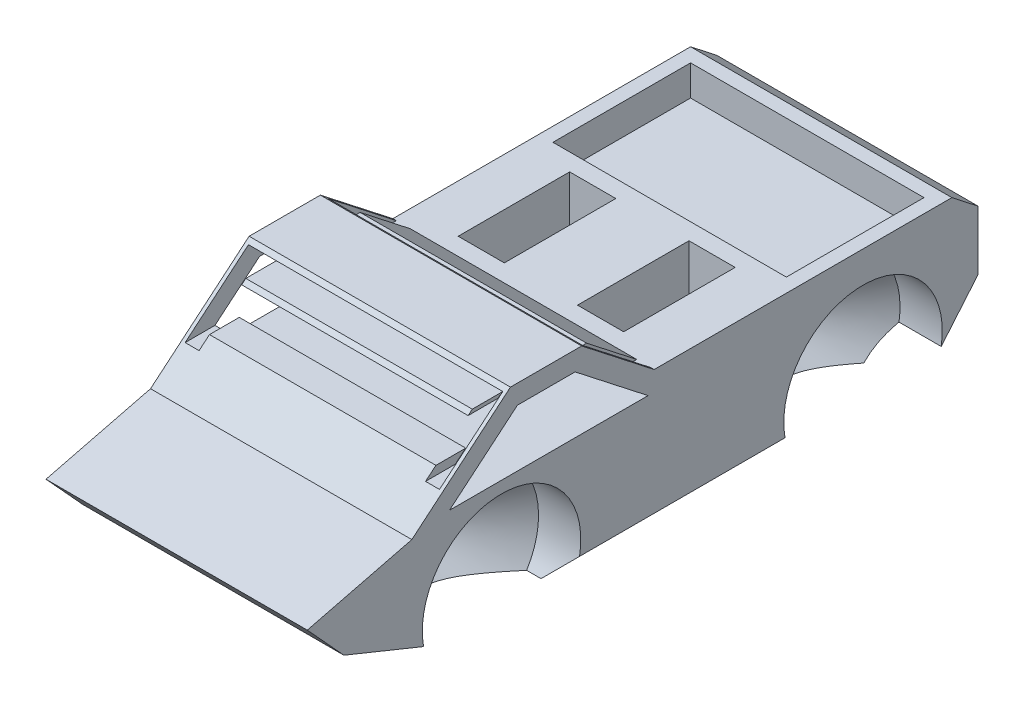
SolidWorks part; units mm, degrees
material "AISI 316 Stainless Steel Sheet (SS)"
ref_plane "Front Plane" through (0, 0, 0) normal (0, 0, 1) x (1, 0, 0)
ref_plane "Top Plane" through (0, 0, 0) normal (0, 1, 0) x (1, 0, 0)
ref_plane "Right Plane" through (0, 0, 0) normal (1, 0, 0) x (0, 0, -1)
sketch "Sketch1" plane through (0, 0, 0) normal (1, 0, 0) x (0, 0, -1)
  line L0 (0, 0) -> (12, 3)
  line L1 (12, 3) -> (23.3217, 12.5)
  line L2 (23.3217, 12.5) -> (31.5, 12.5)
  line L3 (31.5, 12.5) -> (39.8196, 6)
  line L4 (39.8196, 6) -> (74, 6)
  line L5 (74, 6) -> (77, 3.6561)
  line L6 (77, 3.6561) -> (77, -3.1577)
  line L7 (77, -3.1577) -> (70, -11.5)
  line L8 (70, -11.5) -> (16, -11.5)
  line L9 (16, -11.5) -> (13.3149, -8.3)
  line L10 (13.3149, -8.3) -> (4.2, -4.6)
  line L11 (4.2, -4.6) -> (0, 0)
  line L12 (16.3211, 3.754) -> (24.1224, 10.3)
  line L13 (24.1224, 10.3) -> (30.7425, 10.3)
  line L14 (30.7425, 10.3) -> (39.121, 3.754)
  line L15 (30.7425, 10.3) -> (38.4652, 4.2664) construction
  line L17 (13.4141, 1.3147) -> (24.1224, 10.3) construction
  line L18 (16.3211, 3.754) -> (39.121, 3.754)
  dimension "D1" = 12
  dimension "D2" = 31.5
  dimension "D3" = 24
  dimension "D4" = 40
  dimension "D5" = 38
  dimension "D6" = 3
  dimension "D7" = 17.5
  dimension "D8" = 7
  dimension "D9" = 130
  dimension "D10" = 77
  dimension "D11" = 16
  dimension "D12" = 3.2
  dimension "D13" = 4.2
  dimension "D14" = 4.6
  dimension "D15" = 11.5
  dimension "D16" = 3
  dimension "D18" = 22.7999
  dimension "D19" = 2.2
  dimension "D17" = 2.2
extrude "Boss-Extrude1" add sketch "Sketch1" along normal mid plane 30
chamfer "Chamfer1" distance 3.2 angle 45 2 edges at (-15, -11.5, -43) (15, -11.5, -43)
ref_plane "Plane1" through (0, 0, -22.3) normal (0, 0, 1) x (1, 0, 0)
sketch "Sketch2" plane through (0, 0, -22.3) normal (0, 0, 1) x (1, 0, 0)
  line L0 (15, 2.4) -> (10.15, 2.4)
  line L1 (15, 3) -> (15, 0) construction
  line L2 (10.15, 2.4) -> (3.75, -4)
  line L3 (3.75, -4) -> (0, -4)
  line L4 (0, -4) -> (0, -6.7)
  line L5 (0, -6.7) -> (15, -6.7)
  line L6 (15, -4.6) -> (15, -8.3) construction
  line L7 (15, -6.7) -> (15, 2.4)
  line L8 (0, -6.7) -> (-8.558, -6.7) construction
  dimension "D1" = 5.4
  dimension "D2" = 45
  dimension "D3" = 3.75
  dimension "D4" = 6.7
  dimension "D5" = 18.2
revolve "Cut-Revolve1" cut sketch "Sketch2" angle 360 about L8
mirror "Mirror1" about plane through (0, 0, 0) normal (1, 0, 0) of "Cut-Revolve1"
pattern_linear "LPattern1" count 2 spacing 41.5 along (0, 0, -1) of "Cut-Revolve1"
mirror "Mirror2" about plane through (0, 0, 0) normal (1, 0, 0) of "LPattern1"
sketch "Sketch4" plane through (0, 6, 0) normal (0, 1, 0) x (1, 0, 0)
  line L0 (15, 74) -> (15, 39.8196) construction
  line L1 (4.2, 54.6196) -> (9.5, 54.6196)
  line L2 (4.2, 54.6196) -> (4.2, 41.8196)
  line L3 (4.2, 41.8196) -> (9.5, 41.8196)
  line L4 (9.5, 54.6196) -> (9.5, 41.8196)
  line L5 (15, 39.8196) -> (-15, 39.8196) construction
  dimension "D1" = 5.5
  dimension "D2" = 5.3
  dimension "D3" = 12.8
  dimension "D4" = 2
extrude "Cut-Extrude1" cut sketch "Sketch4" against normal through all
mirror "Mirror3" about plane through (0, 0, 0) normal (1, 0, 0) of "Cut-Extrude1"
sketch "Sketch5" plane through (0, 6, 0) normal (0, 1, 0) x (1, 0, 0)
  line L0 (15, 74) -> (15, 39.8196) construction
  line L1 (-13.4, 72.4) -> (13.4, 72.4)
  line L2 (-13.4, 72.4) -> (-13.4, 56.6)
  line L3 (-13.4, 56.6) -> (13.4, 56.6)
  line L4 (13.4, 72.4) -> (13.4, 56.6)
  line L5 (-15, 74) -> (-15, 39.8196) construction
  line L6 (15, 74) -> (-15, 74) construction
  dimension "D1" = 15.8
  dimension "D2" = 1.6
  dimension "D3" = 1.6
  dimension "D4" = 1.6
extrude "Cut-Extrude2" cut sketch "Sketch5" against normal blind 3.5
sketch "Sketch6" plane through (0, 0, 0) normal (0, 0, 1) x (1, 0, 0)
  line L2 (15, 7) -> (-15, 7)
  line L3 (13, 7) -> (-13, 7)
  line L11 (15, 8.5) -> (-15, 8.5)
  line L12 (-13, 10.5) -> (-13, 6)
  line L13 (13, 6) -> (13, 10.5)
  line L14 (13, 10.5) -> (-13, 10.5)
  line L15 (-13, 10.5) -> (-13, 6)
  line L16 (13, 6) -> (13, 10.5)
  line L17 (13, 10.5) -> (-13, 10.5)
  line L18 (13, 8.5) -> (-13, 8.5)
  dimension "D1" = 2
  dimension "D2" = 4
  dimension "D3" = 5.5
extrude "Cut-Extrude-Thin11" cut sketch "Sketch6" against normal up to next thin thin type one direction wall 1.6
